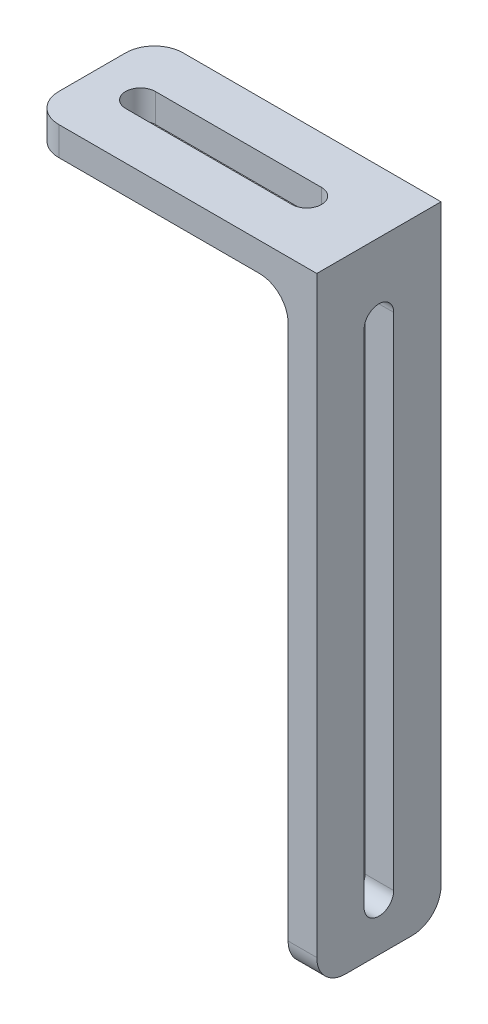
SolidWorks part; units mm, degrees
ref_plane "Front Plane" through (0, 0, 0) normal (0, 0, 1) x (1, 0, 0)
ref_plane "Top Plane" through (0, 0, 0) normal (0, 1, 0) x (1, 0, 0)
ref_plane "Right Plane" through (0, 0, 0) normal (1, 0, 0) x (0, 0, -1)
sketch "Sketch1" plane through (0, 0, 0) normal (0, 0, 1) x (1, 0, 0)
  line L0 (0, 0) -> (3, 0)
  line L1 (3, 0) -> (3, 65)
  line L2 (3, 65) -> (-27, 65)
  line L3 (-27, 65) -> (-27, 62)
  line L4 (-27, 62) -> (0, 62)
  line L5 (0, 62) -> (0, 0)
  dimension "D1" = 27
  dimension "D2" = 65
  dimension "D3" = 3
  dimension "D4" = 3
extrude "Boss-Extrude1" add sketch "Sketch1" along normal blind 13
sketch "Sketch6" plane through (3, 0, 0) normal (1, 0, 0) x (0, 0, -1)
  line L0 (-6.5, 65) -> (-6.5, 0) construction
  line L1 (-13, 65) -> (0, 65) construction
  line L2 (-13, 0) -> (0, 0) construction
  line L3 (-6.5, 57.45) -> (-6.5, 5.05) construction
  line L4 (-4.95, 57.45) -> (-4.95, 5.05)
  line L5 (-8.05, 57.45) -> (-8.05, 5.05)
  arc A0 (-4.95, 57.45) -> (-8.05, 57.45) centre (-6.5, 57.45) ccw
  arc A1 (-8.05, 5.05) -> (-4.95, 5.05) centre (-6.5, 5.05) ccw
  point P8 (-6.5, 31.25)
  point P13 (-6.5, 59)
  point P14 (-6.5, 3.5)
  dimension "D1" = 3.1
  dimension "D2" = 6
  dimension "D3" = 3.5
  dimension "D4" = 55.5
extrude "Cut-Extrude1" cut sketch "Sketch6" against normal through all
sketch "Sketch7" plane through (0, 65, 0) normal (0, 1, 0) x (1, 0, 0)
  line L0 (-27, -6.5) -> (3, -6.5) construction
  line L1 (-27, -13) -> (-27, 0) construction
  line L2 (3, -13) -> (3, 0) construction
  line L3 (-21.95, -6.5) -> (-4.55, -6.5) construction
  line L4 (-21.95, -4.95) -> (-4.55, -4.95)
  line L5 (-21.95, -8.05) -> (-4.55, -8.05)
  arc A0 (-21.95, -4.95) -> (-21.95, -8.05) centre (-21.95, -6.5) ccw
  arc A1 (-4.55, -8.05) -> (-4.55, -4.95) centre (-4.55, -6.5) ccw
  point P8 (-13.25, -6.5)
  point P13 (-23.5, -6.5)
  point P14 (-3, -6.5)
  dimension "D2" = 6
  dimension "D1" = 3.5
  dimension "D3" = 3.1
  dimension "D4" = 20.5
extrude "Cut-Extrude2" cut sketch "Sketch7" against normal through all contours L4 A1 L5 A0
fillet "Fillet1" radius 3 1 edges at (0, 62, 6.5)
fillet "Fillet2" radius 3 4 edges at (1.5, 0, 0) (1.5, 0, 13) (-27, 63.5, 13) (-27, 63.5, 0)
